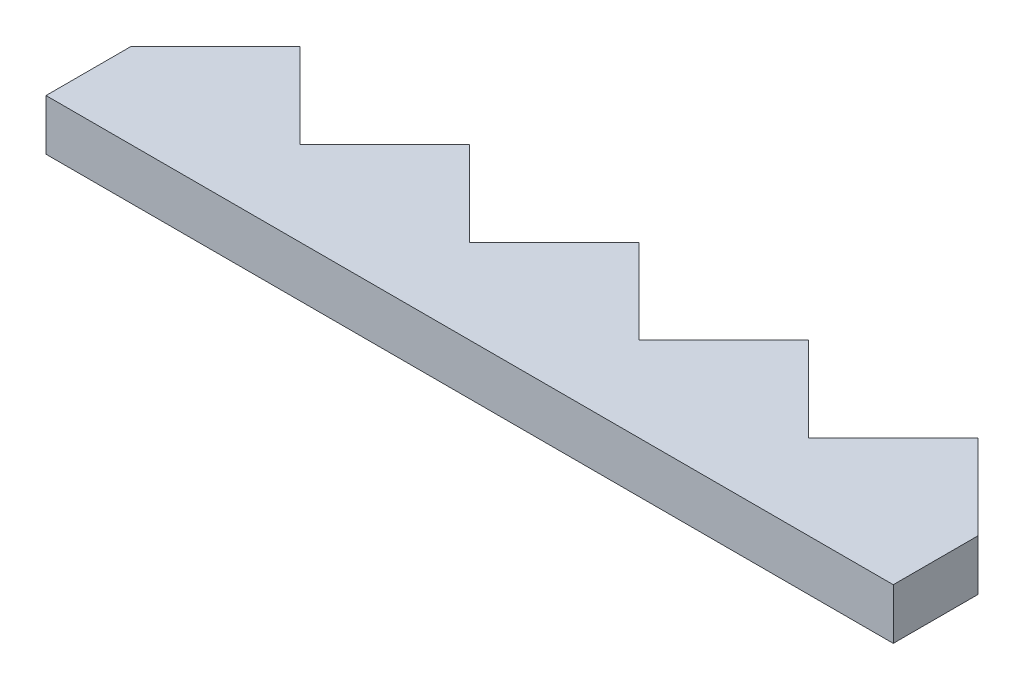
SolidWorks part; units mm, degrees
material "Custom Plastic"
ref_plane "Front Plane" through (0, 0, 0) normal (0, 0, 1) x (1, 0, 0)
ref_plane "Top Plane" through (0, 0, 0) normal (0, 1, 0) x (1, 0, 0)
ref_plane "Right Plane" through (0, 0, 0) normal (1, 0, 0) x (0, 0, -1)
sketch "Sketch1" plane through (0, 0, 0) normal (0, 1, 0) x (1, 0, 0)
  line L0 (0, 5) -> (5, 10)
  line L2 (0, 5) -> (0, 0)
  line L3 (0, 0) -> (50, 0)
  line L5 (5, 10) -> (10, 5)
  line L6 (10, 5) -> (15, 10)
  line L7 (15, 10) -> (20, 5)
  line L8 (20, 5) -> (25, 10)
  line L9 (25, 10) -> (30, 5)
  line L10 (30, 5) -> (35, 10)
  line L11 (35, 10) -> (40, 5)
  line L12 (40, 5) -> (45, 10)
  line L13 (45, 10) -> (50, 5)
  line L18 (5, 10) -> (65, 10) construction
  line L19 (50, 5) -> (50, 0)
  dimension "D1" = 5
  dimension "D2" = 10
  dimension "D4" = 10
  dimension "D5" = 5
extrude "Boss-Extrude1" add sketch "Sketch1" along normal blind 3
